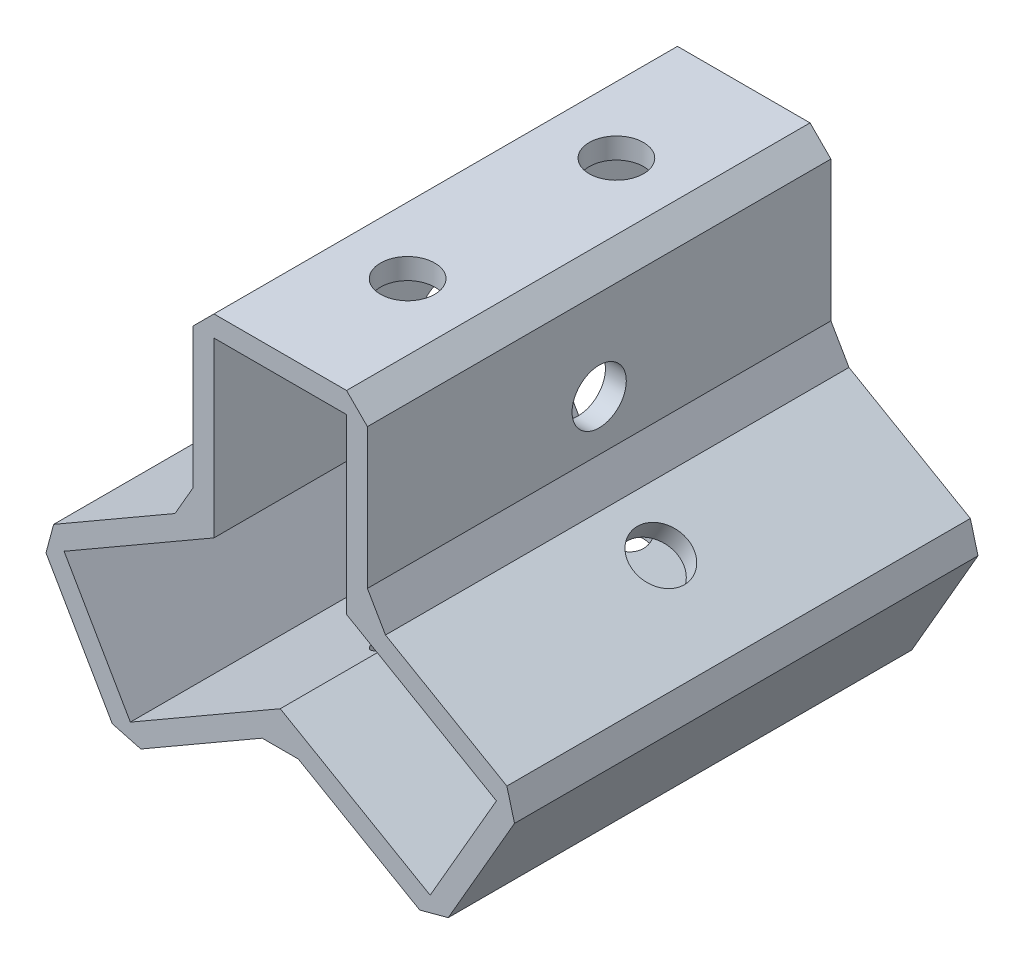
SolidWorks part; units mm, degrees
ref_plane "Front Plane" through (0, 0, 0) normal (0, 0, 1) x (1, 0, 0)
ref_plane "Top Plane" through (0, 0, 0) normal (0, 1, 0) x (1, 0, 0)
ref_plane "Right Plane" through (0, 0, 0) normal (1, 0, 0) x (0, 0, -1)
sketch "Sketch1" plane through (0, 0, 0) normal (0, 0, 1) x (1, 0, 0)
  line L0 (0, 0) -> (0, 6.3532) construction
  line L2 (-6.35, 3.6662) -> (-6.35, 20.2462)
  line L3 (-6.35, 20.2462) -> (6.35, 20.2462)
  line L4 (6.35, 3.6662) -> (6.35, 20.2462)
  line L5 (0, 0) -> (-1.6441, 0.9492) construction
  line L6 (0, 0) -> (-5.4993, -3.175) construction
  line L7 (0, 6.3532) -> (6.35, 6.3532) construction
  line L8 (-1.6441, 0.9492) -> (-4.8191, -4.55) construction
  line L9 (-5.4993, -3.175) -> (-8.6743, 2.3243) construction
  line L10 (-20.7087, -4.6238) -> (-6.35, 3.6662)
  line L11 (-20.7087, -4.6238) -> (-14.3587, -15.6223)
  line L12 (-14.3587, -15.6223) -> (0, -7.3323)
  line L13 (14.3587, -15.6223) -> (20.7087, -4.6238)
  line L14 (0, -7.3323) -> (14.3587, -15.6223)
  line L15 (20.7087, -4.6238) -> (6.35, 3.6662)
  line L16 (-8.35, 4.8209) -> (-8.35, 22.2462)
  line L17 (-8.35, 22.2462) -> (8.35, 22.2462)
  line L18 (8.35, 4.8209) -> (8.35, 22.2462)
  line L19 (23.4408, -3.8918) -> (8.35, 4.8209)
  line L20 (15.0908, -18.3544) -> (23.4408, -3.8918)
  line L21 (0, -9.6417) -> (15.0908, -18.3544)
  line L22 (-15.0908, -18.3544) -> (0, -9.6417)
  line L23 (-23.4408, -3.8918) -> (-15.0908, -18.3544)
  line L24 (-23.4408, -3.8918) -> (-8.35, 4.8209)
  line L25 (-10.5077, 0.111) -> (-5.1577, -9.1555)
  line L26 (0.2127, -7.2095) -> (-0.2873, -6.3435) construction
  line L27 (-5.6373, 2.923) -> (-19.8815, -5.3009)
  line L28 (-0.2873, -6.3435) -> (-14.5315, -14.5674)
  line L29 (-5.6373, 2.923) -> (0, 0) construction
  line L30 (0, 0) -> (-0.2873, -6.3435) construction
  line L31 (-19.8815, -5.3009) -> (-20.1688, -11.6444) construction
  line L32 (-20.1688, -11.6444) -> (-14.5315, -14.5674) construction
  line L33 (-12.7594, -1.189) -> (-7.4094, -10.4555) construction
  line L34 (-12.7594, -1.189) -> (-8.7983, 1.098)
  line L36 (-12.7594, -1.189) -> (-14.2594, 1.4091) construction
  line L37 (-5.35, 3.4205) -> (-5.35, 19.8684)
  line L38 (5.35, 3.4205) -> (5.35, 19.8684)
  line L39 (5.35, 11.6444) -> (-5.35, 11.6444) construction
  line L40 (5.35, 11.6444) -> (8.35, 11.6444) construction
  line L41 (3.35, 9.0444) -> (-5.35, 9.0444)
  line L42 (5.6373, 2.923) -> (19.8815, -5.3009)
  line L43 (0.2873, -6.3435) -> (14.5315, -14.5674)
  line L44 (7.4094, -10.4555) -> (12.7594, -1.189) construction
  line L45 (7.4094, -10.4555) -> (5.9094, -13.0535) construction
  line L46 (6.1577, -7.4234) -> (10.5077, 0.111)
  line L47 (7.4094, -10.4555) -> (5.9094, -13.0535) construction
  arc A0 (-5.6373, 2.923) -> (-0.2873, -6.3435) centre (0, 0) ccw construction
  arc A2 (-5.6373, 2.923) -> (-0.2873, -6.3435) centre (0, 0) ccw
  circle A3 centre (0, 0) radius 6.35 construction
  arc A4 (-14.5315, -14.5674) -> (-19.8815, -5.3009) centre (-20.1688, -11.6444) ccw
  arc A5 (-5.35, 19.8684) -> (5.35, 19.8684) centre (0, 23.2889) ccw
  arc A6 (5.35, 3.4205) -> (-5.35, 3.4205) centre (0, 0) ccw
  arc A7 (19.8815, -5.3009) -> (14.5315, -14.5674) centre (20.1688, -11.6444) ccw
  arc A8 (0.2873, -6.3435) -> (5.6373, 2.923) centre (0, 0) ccw
  point P64 (0, 0)
  dimension "D1" = 2
  dimension "D19" = 12.7
  dimension "D2" = 120
  dimension "D3" = 120
  dimension "D4" = 120
  dimension "D5" = 6.35
  dimension "D6" = 6.35
  dimension "D7" = 6.35
  dimension "D8" = 12.7
  dimension "D9" = 16.58
  dimension "D10" = 16.58
  dimension "D11" = 16.58
  dimension "D12" = 16.58
  dimension "D13" = 16.58
  dimension "D14" = 16.58
  dimension "D15" = 1
  dimension "D16" = 1
  dimension "D17" = 2.6
  dimension "D20" = 3
extrude "Boss-Extrude1" add sketch "Sketch1" along normal blind 44.4 contours L24 L23 L22 L21 L20 L19 L18 L17 L16 L15 L13 L14 L12 L11 L10 L2 L3 L4 region at (-7.7298, 13.5335, 0)
sketch "Sketch4" plane through (-4.175, 7.2313, 0) normal (-0.5, 0.866, 0) x (0.866, 0.5, 0)
  line L0 (-11.6444, 0) -> (-11.6444, -44.4) construction
  line L2 (-22.2462, -44.4) -> (-4.8209, -44.4) construction
  circle A0 centre (-11.6444, -22.2) radius 2.6
  dimension "D1" = 5.2
extrude "Cut-Extrude1" cut sketch "Sketch4" against normal through all
sketch "Sketch5" plane through (0, 0, 0) normal (0, 1, 0) x (1, 0, 0)
  line L0 (0, 0) -> (0, -44.4) construction
sketch "Sketch6" plane through (0, 22.2462, 0) normal (0, 1, 0) x (1, 0, 0)
  line L0 (0, -22.2) -> (0, -12.2) construction
  line L1 (0, 200000) -> (0, -200044.4) construction
  line L2 (0, -22.2) -> (0, -32.2) construction
  circle A0 centre (0, -12.2) radius 2.6
  circle A1 centre (0, -32.2) radius 2.6
  dimension "D2" = 5.2
  dimension "D4" = 5.2
  dimension "D1" = 10
  dimension "D3" = 10
extrude "Cut-Extrude2" cut sketch "Sketch6" against normal through all
chamfer "Chamfer1" distance 2 distance2 2 11 edges at (-8.35, 4.8209, 22.2) (-8.35, 22.2462, 22.2) (8.35, 22.2462, 22.2) (8.35, 4.8209, 22.2) (23.4408, -3.8918, 22.2) (0, -9.6417, 4.8) (0, -9.6417, 22.2) (15.0908, -18.3544, 22.2) (0, -9.6417, 39.6) (-23.4408, -3.8918, 22.2) (-15.0908, -18.3544, 22.2) tangent propagation no
sketch "Sketch7" plane through (8.35, 0, 0) normal (1, 0, 0) x (0, 0, -1)
  line L0 (0, 11.6444) -> (-44.4, 11.6444) construction
  line L1 (-44.4, 6.8209) -> (-44.4, 20.2462) construction
  circle A0 centre (-22.2, 11.6444) radius 2.6
  dimension "D1" = 5.2
extrude "Cut-Extrude3" cut sketch "Sketch7" against normal through all
sketch "Sketch9" plane through (-4.175, -7.2313, 0) normal (-0.5, -0.866, 0) x (0.866, -0.5, 0)
  line L0 (11.6444, 0) -> (11.6444, 44.4) construction
  line L1 (6.8209, 44.4) -> (20.2462, 44.4) construction
  circle A0 centre (11.6444, 22.2) radius 2.6
  dimension "D1" = 5.2
extrude "Cut-Extrude4" cut sketch "Sketch9" against normal through all
